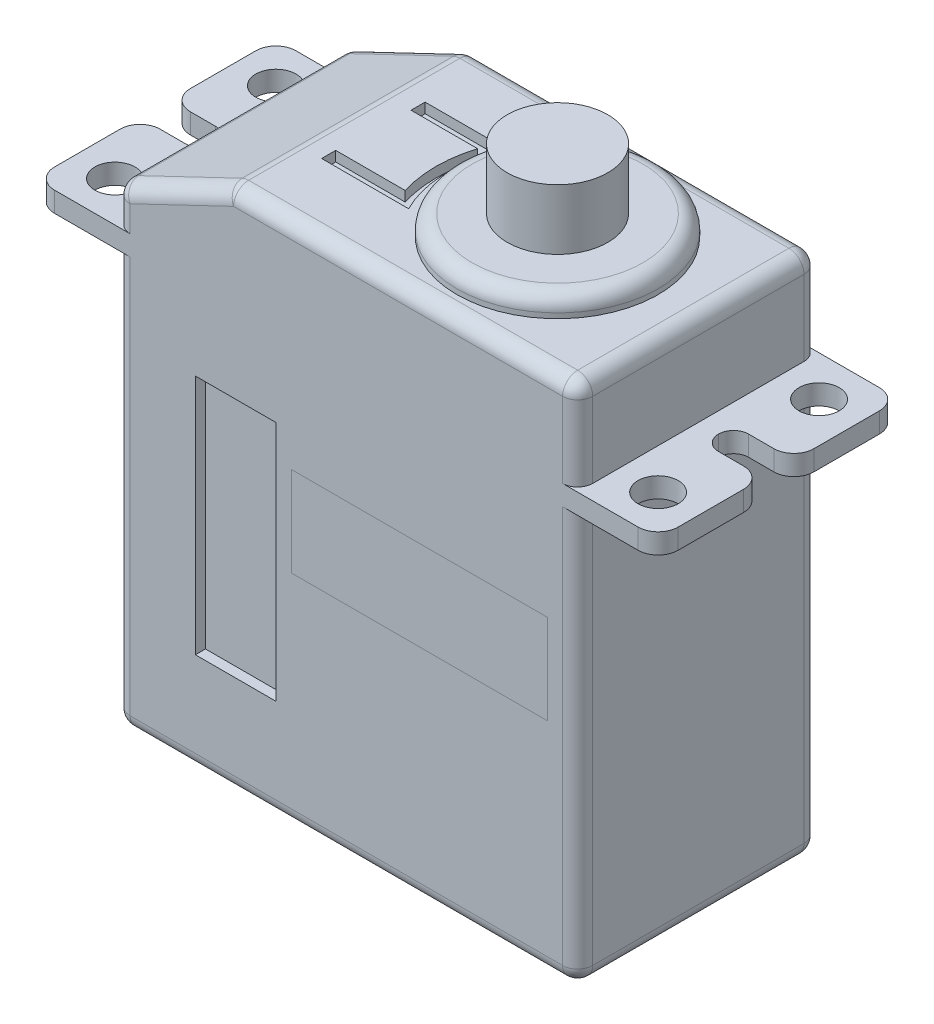
SolidWorks part; units mm, degrees
ref_plane "Front Plane" through (0, 0, 0) normal (0, 0, 1) x (1, 0, 0)
ref_plane "Top Plane" through (0, 0, 0) normal (0, 1, 0) x (1, 0, 0)
ref_plane "Right Plane" through (0, 0, 0) normal (1, 0, 0) x (0, 0, -1)
sketch "Sketch1" plane through (0, 0, 0) normal (0, 0, 1) x (1, 0, 0)
  line L1 (0, 0) -> (23, 0)
  line L2 (0, 0) -> (0, 26)
  line L3 (0, 26) -> (23, 26)
  line L4 (23, 0) -> (23, 26)
  dimension "D1" = 26
  dimension "D2" = 23
extrude "Boss-Extrude1" add sketch "Sketch1" along normal blind 12
sketch "Sketch2" plane through (0, 0, 12) normal (0, 0, 1) x (1, 0, 0)
  line L0 (5.726, 26) -> (0, 23.2609)
  line L1 (23, 26) -> (0, 26) construction
  line L2 (0, 26) -> (0, 0) construction
  line L3 (0, 23.2609) -> (0, 26)
  line L4 (0, 26) -> (5.726, 26)
extrude "Cut-Extrude1" cut sketch "Sketch2" against normal blind 12
sketch "Sketch3" plane through (0, 0, 0) normal (-1, 0, 0) x (0, 0, 1)
  line L0 (0, 23.2609) -> (0, 0) construction
  line L1 (0, 21.5) -> (12, 21.5)
  line L2 (0, 21.5) -> (0, 20.5)
  line L3 (0, 20.5) -> (12, 20.5)
  line L4 (12, 21.5) -> (12, 20.5)
  line L5 (12, 23.2609) -> (12, 0) construction
  line L6 (12, 0) -> (0, 0) construction
  dimension "D1" = 1
  dimension "D2" = 20.5
extrude "Boss-Extrude2" add sketch "Sketch3" along normal blind 4 and the other way blind 27
sketch "Sketch5" plane through (0, 21.5, 0) normal (0, 1, 0) x (1, 0, 0)
  line L0 (0, 0) -> (-4, 0) construction
  line L1 (27, 0) -> (23, 0) construction
  line L2 (0, -12) -> (-4, -12) construction
  line L3 (27, -12) -> (23, -12) construction
  circle A0 centre (-2, -10) radius 1
  circle A1 centre (-2, -2) radius 1
  circle A2 centre (25, -2) radius 1
  circle A3 centre (25, -10) radius 1
  point P10 (-2, 0)
  point P13 (25, 0)
  dimension "D5" = 2
  dimension "D1" = 2
  dimension "D2" = 2
  dimension "D3" = 2
  dimension "D4" = 2
extrude "Cut-Extrude2" cut sketch "Sketch5" against normal blind 5
sketch "Sketch6" plane through (0, 21.5, 0) normal (0, 1, 0) x (1, 0, 0)
  line L0 (-4, -12) -> (-4, 0) construction
  line L1 (-4, -5.25) -> (-1, -5.25)
  line L2 (-4, -5.25) -> (-4, -6.75)
  line L3 (-4, -6.75) -> (-1, -6.75)
  line L4 (-1, -5.25) -> (-1, -6.75)
  line L5 (27, -12) -> (27, 0) construction
  line L6 (27, -5.25) -> (24, -5.25)
  line L7 (27, -5.25) -> (27, -6.75)
  line L8 (27, -6.75) -> (24, -6.75)
  line L9 (24, -5.25) -> (24, -6.75)
  point P12 (-4, -6)
  point P13 (-1, -6)
  point P14 (27, -6)
  point P15 (24, -6)
  dimension "D1" = 1.5
  dimension "D2" = 1.5
  dimension "D3" = 3
  dimension "D4" = 3
extrude "Cut-Extrude3" cut sketch "Sketch6" against normal blind 5
fillet "Fillet1" radius 1 8 edges at (-4, 21, 5.25) (27, 21, 0) (27, 21, 5.25) (27, 21, 6.75) (27, 21, 12) (-4, 21, 12) (-4, 21, 6.75) (-4, 21, 0)
fillet "Fillet2" radius 0.75 4 edges at (-1, 21, 6.75) (-1, 21, 5.25) (24, 21, 6.75) (24, 21, 5.25)
sketch "Sketch7" plane through (0, 26, 0) normal (0, 1, 0) x (1, 0, 0)
  line L0 (23, -12) -> (23, 0) construction
  line L1 (23, -12) -> (23, 0) construction
  circle A0 centre (16, -6) radius 5
  point P4 (23, -6)
  dimension "D1" = 10
  dimension "D2" = 7
extrude "Boss-Extrude3" add sketch "Sketch7" along normal blind 1
sketch "Sketch8" plane through (0, 26, 0) normal (0, 1, 0) x (1, 0, 0)
  line L0 (11.1019, -3.5) -> (6.9174, -3.5)
  line L1 (6.9174, -3.5) -> (6.9174, -4.2)
  line L2 (6.9174, -4.2) -> (10.2291, -4.2)
  line L3 (6.7735, -8.5) -> (11.1019, -8.5)
  line L4 (6.7735, -8.5) -> (6.7735, -7.8)
  line L5 (6.7735, -7.8) -> (10.2291, -7.8)
  line L6 (23, 0) -> (5.726, 0) construction
  line L7 (23, -12) -> (5.726, -12) construction
  arc A0 (11.1019, -3.5) -> (11.1019, -8.5) centre (16, -6) ccw
  arc A1 (10.2291, -4.2) -> (10.2291, -7.8) centre (16, -6) ccw
  dimension "D1" = 0.7
  dimension "D2" = 0.7
  dimension "D3" = 3.5
  dimension "D4" = 3.5
extrude "Cut-Extrude4" cut sketch "Sketch8" against normal blind 0.5
fillet "Fillet3" radius 0.75 20 edges at (23, 0, 6) (11.5, 0, 12) (0, 0, 6) (0, 22.3805, 0) (0, 22.3805, 12) (0, 10.25, 12) (0, 10.25, 0) (11.5, 0, 0) (23, 26, 6) (23, 23.75, 12) (23, 10.25, 12) (23, 10.25, 0) (23, 23.75, 0) (16, 27, 11) (14.363, 26, 12) (2.863, 24.6305, 12) (0, 23.2609, 6) (2.863, 24.6305, 0) (5.726, 26, 6) (14.363, 26, 0)
sketch "Sketch9" plane through (0, 0, 12) normal (0, 0, 1) x (1, 0, 0)
  line L0 (22.25, 0) -> (0.75, 0) construction
  line L1 (4, 17) -> (8, 17)
  line L2 (4, 17) -> (4, 5)
  line L3 (4, 5) -> (8, 5)
  line L4 (8, 17) -> (8, 5)
  line L5 (0, 0.75) -> (0, 20.5) construction
  dimension "D1" = 12
  dimension "D2" = 4
  dimension "D3" = 5
  dimension "D4" = 4
extrude "Cut-Extrude5" cut sketch "Sketch9" against normal blind 0.5
sketch "Sketch10" plane through (0, 27, 0) normal (0, 1, 0) x (1, 0, 0)
  circle A0 centre (16, -6) radius 2.5
  dimension "D1" = 5
extrude "Boss-Extrude4" add sketch "Sketch10" along normal blind 3
sketch "Sketch11" plane through (0, 0, 12) normal (0, 0, 1) x (1, 0, 0)
  line L1 (8.7709, 15.3612) -> (21.4934, 15.3612)
  line L2 (8.7709, 15.3612) -> (8.7709, 10.9063)
  line L3 (8.7709, 10.9063) -> (21.4934, 10.9063)
  line L4 (21.4934, 15.3612) -> (21.4934, 10.9063)
split line "Split Line1"
sketch "Sketch12" plane through (0, 0, 0) normal (0, -1, 0) x (1, 0, 0)
  line L0 (0, 11.25) -> (0, 0.75) construction
  line L1 (23, 0.75) -> (23, 11.25) construction
  line L2 (0.75, 12) -> (22.25, 12) construction
  line L3 (5.8962, 0) -> (22.25, 0) construction
  circle A0 centre (-2, 10) radius 1 construction
  circle A1 centre (25, 10) radius 1 construction
